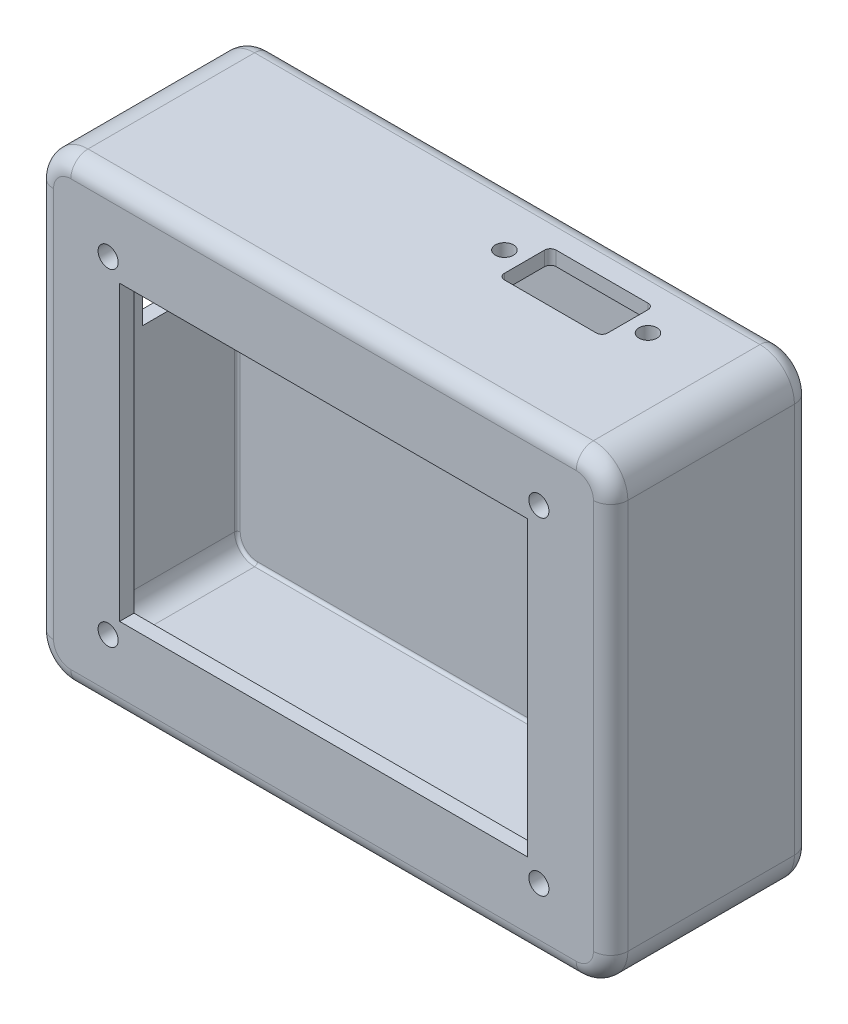
SolidWorks part; units mm, degrees
ref_plane "Vehicle Ground Plane" through (0, 0, 0) normal (0, 0, 1) x (1, 0, 0)
ref_plane "Vehicle Centreline Plane" through (0, 0, 0) normal (0, 1, 0) x (1, 0, 0)
ref_plane "Roll Hoop Plane" through (0, 0, 0) normal (1, 0, 0) x (0, 0, -1)
ref_axis "X-Axis" through (-88.99, 0, 0) along (1, 0, 0)
ref_axis "Y-Axis" through (0, 55, 0) along (0, -1, 0)
ref_axis "Z-Axis" through (0, 0, -88.99) along (0, 0, 1)
sketch "Sketch1" plane through (0, 0, 0) normal (0, 0, 1) x (1, 0, 0)
  line L1 (-50, -40) -> (50, -40)
  line L2 (-50, -40) -> (-50, 40)
  line L3 (-50, 40) -> (50, 40)
  line L4 (50, -40) -> (50, 40)
  line L5 (-50, -40) -> (50, 40) construction
  line L6 (-50, 40) -> (50, -40) construction
  point P0 (0, 0)
  dimension "D1" = 100
  dimension "D2" = 80
extrude "Boss-Extrude1" add sketch "Sketch1" along normal mid plane 35
fillet "Fillet1" radius 6 4 edges at (-50, 40, 0) (-50, -40, 0) (50, -40, 0) (50, 40, 0)
fillet "Fillet2" radius 3 16 edges at (48.2426, -38.2426, 17.5) (0, -40, 17.5) (-48.2426, -38.2426, 17.5) (-50, 0, 17.5) (-48.2426, 38.2426, 17.5) (0, 40, 17.5) (48.2426, 38.2426, 17.5) (48.2426, 38.2426, -17.5) (50, 0, -17.5) (48.2426, -38.2426, -17.5) (0, -40, -17.5) (-48.2426, -38.2426, -17.5) (-50, 0, -17.5) (-48.2426, 38.2426, -17.5) (50, 0, 17.5) (0, 40, -17.5)
shell "Shell1" thickness 2.5
sketch "Sketch2" plane through (0, 0, 17.5) normal (0, 0, 1) x (1, 0, 0)
  line L1 (35.5, 25.5) -> (-35.5, 25.5)
  line L2 (35.5, 25.5) -> (35.5, -25.5)
  line L3 (35.5, -25.5) -> (-35.5, -25.5)
  line L4 (-35.5, 25.5) -> (-35.5, -25.5)
  line L5 (35.5, 25.5) -> (-35.5, -25.5) construction
  line L6 (35.5, -25.5) -> (-35.5, 25.5) construction
  circle A0 centre (37.5, -28.5) radius 1.75
  circle A1 centre (-37.5, -28.5) radius 1.75
  circle A2 centre (-37.5, 28.5) radius 1.75
  circle A3 centre (37.5, 28.5) radius 1.75
  point P0 (0, 0)
  point P14 (0, 0)
  point P15 (0, 0)
  point P16 (29.1985, -18.5387)
  dimension "D3" = 3.5
  dimension "D1" = 71
  dimension "D2" = 51
  dimension "D4" = 75
  dimension "D5" = 57
  dimension "D6" = 28.5
  dimension "D7" = 37.5
extrude "Cut-Extrude1" cut sketch "Sketch2" against normal up to next
sketch "Sketch4" plane through (0, 40, 0) normal (0, 1, 0) x (1, 0, 0)
  line L0 (-44, 17.5) -> (44, 17.5) construction
  line L1 (29, 11) -> (11, 11)
  line L2 (29, 11) -> (29, 2)
  line L3 (29, 2) -> (11, 2)
  line L4 (11, 11) -> (11, 2)
  line L5 (29, 11) -> (11, 2) construction
  line L6 (29, 2) -> (11, 11) construction
  line L7 (50, 14.5) -> (50, -14.5) construction
  circle A0 centre (32.5, 6.5) radius 1.575
  circle A1 centre (7.5, 6.5) radius 1.575
  point P4 (20, 6.5)
  dimension "D1" = 3.15
  dimension "D2" = 18
  dimension "D3" = 25
  dimension "D4" = 9
  dimension "D5" = 11
  dimension "D6" = 30
  dimension "D7" = 12.5
extrude "Cut-Extrude2" cut sketch "Sketch4" against normal up to next
fillet "Fillet4" radius 1 4 edges at (11, 38.75, -11) (11, 38.75, -2) (29, 38.75, -2) (29, 38.75, -11)
sketch "Sketch5" plane through (-50, 0, 0) normal (-1, 0, 0) x (0, 0, 1)
  line L0 (-17.5, -34) -> (-17.5, 34) construction
  line L1 (-11.5, 24.9) -> (1.5, 24.9)
  line L2 (-11.5, 24.9) -> (-11.5, 5.1)
  line L3 (-11.5, 5.1) -> (1.5, 5.1)
  line L4 (1.5, 24.9) -> (1.5, 5.1)
  line L5 (-11.5, 24.9) -> (1.5, 5.1) construction
  line L6 (-11.5, 5.1) -> (1.5, 24.9) construction
  line L7 (-14.5, 40) -> (14.5, 40) construction
  point P0 (-5, 15)
  dimension "D1" = 19.8
  dimension "D2" = 13
  dimension "D3" = 12.5
  dimension "D4" = 25
extrude "Cut-Extrude3" cut sketch "Sketch5" against normal up to next
equation "\"D6@Sketch2\"=\"D5@Sketch2\"/2"
equation "\"D7@Sketch2\"=\"D4@Sketch2\"/2"
equation "\"D7@Sketch4\"=\"D3@Sketch4\"/2"
